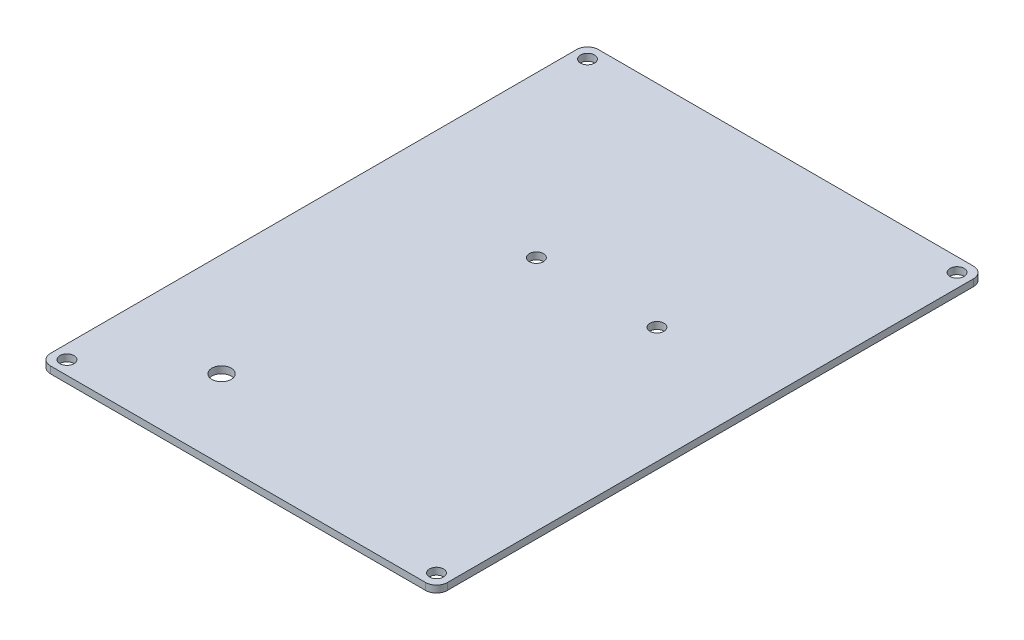
SolidWorks part; units mm, degrees
ref_plane "Front" through (0, 0, 0) normal (0, 0, 1) x (1, 0, 0)
ref_plane "Top" through (0, 0, 0) normal (0, 1, 0) x (1, 0, 0)
ref_plane "Right" through (0, 0, 0) normal (1, 0, 0) x (0, 0, -1)
sketch "Sketch1" plane through (0, 0, 0) normal (0, 1, 0) x (1, 0, 0)
  line L1 (-46, -63.5) -> (46, -63.5)
  line L2 (-46, -63.5) -> (-46, 63.5)
  line L3 (-46, 63.5) -> (46, 63.5)
  line L4 (46, -63.5) -> (46, 63.5)
  line L5 (-46, -63.5) -> (46, 63.5) construction
  line L6 (-46, 63.5) -> (46, -63.5) construction
  point P0 (0, 0)
  dimension "D1" = 127
  dimension "D2" = 92
extrude "Boss-Extrude1" add sketch "Sketch1" along normal blind 1.6
hole_wizard "#4 Clearance Hole2" positions "Sketch2" profile "Sketch3" hole size "#4" standard "ANSI Inch"
sketch "Sketch2" plane through (0, 1.6, 0) normal (0, 1, 0) x (1, 0, 0)
  line L1 (-42.825, 60.325) -> (42.825, 60.325)
  line L2 (-42.825, 60.325) -> (-42.825, -60.325)
  line L3 (-42.825, -60.325) -> (42.825, -60.325)
  line L4 (42.825, 60.325) -> (42.825, -60.325)
  line L5 (-42.825, 60.325) -> (42.825, -60.325) construction
  line L6 (-42.825, -60.325) -> (42.825, 60.325) construction
  line L9 (46, -63.5) -> (46, 63.5) construction
  line L10 (-46, -63.5) -> (46, -63.5) construction
  point P0 (-42.825, 60.325)
  point P2 (42.825, 60.325)
  point P4 (42.825, -60.325)
  point P6 (-42.825, -60.325)
  point P111 (0, 0)
  dimension "D1" = 3.175
  dimension "D2" = 3.175
sketch "Sketch3" plane through (-42.825, 1.6, -60.325) normal (1, 0, 0) x (0, 0, 1)
  line L0 (0, 0) -> (0, 50.9806)
  line L1 (0, 50.9806) -> (1.6319, 50)
  line L2 (1.6319, 50) -> (1.6319, 0)
  line L5 (1.6319, 0) -> (0, 0)
  line L10 (0, 50.9806) -> (-1.632, 50) construction
  line L11 (0, -6.35) -> (0, 107.95) construction
  dimension "Hole Dia." = 3.2639
  dimension "Hole Depth" = 50
  dimension "Drill Angle" = 118
fillet "Fillet1" radius 2.54 4 edges at (46, 0.8, 63.5) (46, 0.8, -63.5) (-46, 0.8, -63.5) (-46, 0.8, 63.5)
hole_wizard "#4 Clearance Hole1" positions "Sketch4" profile "Sketch5" hole size "#4" standard "ANSI Inch"
sketch "Sketch4" plane through (0, 1.6, 0) normal (0, 1, 0) x (1, 0, 0)
  line L1 (46, -60.96) -> (46, 60.96) construction
  line L2 (43.46, 63.5) -> (-43.46, 63.5) construction
  line L3 (-46, 60.96) -> (-46, -60.96) construction
  point P22 (19.05, 14.54)
  point P24 (-8.89, 14.54)
  dimension "D1" = 26.95
  dimension "D2" = 48.96
  dimension "D3" = 48.96
  dimension "D4" = 37.11
sketch "Sketch5" plane through (19.05, 1.6, -14.54) normal (1, 0, 0) x (0, 0, 1)
  line L0 (0, 0) -> (0, 19.7306)
  line L1 (0, 19.7306) -> (1.6319, 18.75)
  line L2 (1.6319, 18.75) -> (1.6319, 0)
  line L5 (1.6319, 0) -> (0, 0)
  line L10 (0, 19.7306) -> (-1.632, 18.75) construction
  line L11 (0, -6.35) -> (0, 107.95) construction
  dimension "Hole Dia." = 3.2639
  dimension "Hole Depth" = 18.75
  dimension "Drill Angle" = 118
hole_wizard "#8 Clearance Hole1" positions "Sketch6" profile "Sketch7" hole size "#8" standard "ANSI Inch"
sketch "Sketch6" plane through (0, 0, 0) normal (0, -1, 0) x (-1, 0, 0)
  circle A0 centre (22.07, -45.25) radius 1.5 construction
  point P0 (22.07, -45.25)
sketch "Sketch7" plane through (-22.07, 0, 45.25) normal (1, 0, 0) x (0, 0, -1)
  line L0 (0, 0) -> (0, 20.1007)
  line L1 (0, 20.1007) -> (2.2479, 18.75)
  line L2 (2.2479, 18.75) -> (2.2479, 0)
  line L5 (2.2479, 0) -> (0, 0)
  line L10 (0, 20.1007) -> (-2.2479, 18.75) construction
  line L11 (0, -6.35) -> (0, 107.95) construction
  dimension "Hole Dia." = 4.4958
  dimension "Hole Depth" = 18.75
  dimension "Drill Angle" = 118
ref_point "PCB_ORIGIN"
sketch "TOP_KEEPOUT" plane through (0, 1.6, 0) normal (0, 1, 0) x (1, 0, 0)
  circle A0 centre (-8.89, 14.54) radius 3.429
  circle A1 centre (19.05, 14.54) radius 3.429
  circle A2 centre (42.825, 60.325) radius 3.429
  circle A3 centre (-42.825, 60.325) radius 3.429
  circle A4 centre (42.825, -60.325) radius 3.429
  circle A5 centre (-42.825, -60.325) radius 3.429
  dimension "D1" = 6.858
sketch "BOTTOM_KEEPOUT" plane through (0, 0, 0) normal (0, -1, 0) x (1, 0, 0)
  line L0 (-26.67, -46.036) -> (-26.67, -3.11) construction
  line L1 (26.67, -47.56) -> (-26.67, -47.56)
  line L2 (26.67, -47.56) -> (26.67, 51.5)
  line L3 (26.67, 51.5) -> (-21.67, 51.5)
  line L4 (-26.67, -47.56) -> (-26.67, 41.5)
  line L7 (-13.716, -47.56) -> (-25.146, -47.56) construction
  line L9 (26.67, -3.11) -> (26.67, -46.56) construction
  line L10 (-25.67, 51.5) -> (25.67, 51.5) construction
  line L11 (-21.67, 51.5) -> (-21.67, 41.5)
  line L12 (-21.67, 41.5) -> (-26.67, 41.5)
  circle A0 centre (-42.825, 60.325) radius 3.937
  circle A1 centre (42.825, 60.325) radius 3.937
  circle A2 centre (42.825, -60.325) radius 3.937
  circle A3 centre (-42.825, -60.325) radius 3.937
  point P13 (0, 0)
  point P20 (26.67, 51.5)
  point P24 (-22.6015, 40.7342)
  dimension "D1" = 7.874
  dimension "D4" = 5
  dimension "D5" = 10
sketch "TOP_CONN_POS" plane through (0, 1.6, 0) normal (0, 1, 0) x (1, 0, 0)
  line L0 (6.35, -35.308) -> (6.35, -45.308)
  line L1 (-37.936, 28.7076) -> (-37.936, 18.7076)
  line L2 (1.35, -40.308) -> (11.35, -40.308)
  line L3 (-42.936, 23.7076) -> (-32.936, 23.7076)
  line L4 (0, 60.436) -> (0, 50.436)
  line L5 (-5, 55.436) -> (5, 55.436)
  line L6 (-37.936, -5.35) -> (-37.936, 52.7652) construction
  line L7 (-43.524, 23.7076) -> (-32.348, 23.7076) construction
  line L8 (0, 61.024) -> (0, 49.848) construction
  line L9 (-29.0576, 55.436) -> (29.0576, 55.436) construction
  line L10 (37.936, 28.7076) -> (37.936, 18.7076)
  line L11 (32.936, 23.7076) -> (42.936, 23.7076)
  line L12 (43.524, 23.7076) -> (32.348, 23.7076) construction
  line L13 (37.936, 52.7652) -> (37.936, -5.35) construction
  line L14 (37.936, -25.0576) -> (37.936, -35.0576)
  line L15 (32.936, -30.0576) -> (42.936, -30.0576)
  line L16 (37.936, -52.7652) -> (37.936, -7.35) construction
  line L17 (43.524, -30.0576) -> (32.348, -30.0576) construction
  line L18 (0, -50.436) -> (0, -60.436)
  line L19 (-5, -55.436) -> (5, -55.436)
  line L20 (29.0576, -55.436) -> (-29.0576, -55.436) construction
  line L21 (0, -61.024) -> (0, -49.848) construction
  line L22 (6.35, -45.896) -> (6.35, -34.72) construction
  line L23 (-16.3576, -40.308) -> (29.0576, -40.308) construction
  point P2 (6.35, -40.308)
  point P5 (0, 0)
  point P6 (-75.0041, 40.9828)
  point P9 (-37.936, 23.7076)
  point P14 (0, 55.436)
  point P17 (-115.78, 17.4589)
  point P18 (-73.2788, 17.3608)
  point P29 (37.936, 23.7076)
  point P32 (73.9745, 24.9368)
  point P40 (37.936, -30.0576)
  point P43 (63.9134, -24.821)
  point P50 (0, -55.436)
  point P53 (6.0715, -69.3479)
  dimension "D1" = 10
  dimension "D2" = 0
  dimension "D3" = 0
  dimension "D4" = 0
  dimension "D5" = 0
  dimension "D6" = 0
  dimension "D7" = 0
  dimension "D8" = 0
  dimension "D9" = 0
  dimension "D10" = 0
  dimension "D11" = 0
  dimension "D12" = 0
  dimension "D13" = 0
sketch "BOTTOM_CONN_POS" plane through (0, 1.6, 0) normal (0, 1, 0) x (1, 0, 0)
  line L0 (0, 12.768) -> (0, -17.232)
  line L1 (-15, -2.232) -> (15, -2.232)
  line L2 (-41.4, 47.425) -> (-41.4, 37.425)
  line L3 (-46.4, 42.425) -> (-36.4, 42.425)
  line L4 (-46, 42.425) -> (-30.6, 42.425) construction
  line L5 (-41.4, 50.75) -> (-41.4, 34.1) construction
  line L6 (-41.4, 28.775) -> (-41.4, 18.775)
  line L7 (-46.4, 23.775) -> (-36.4, 23.775)
  line L8 (-41.4, 13.125) -> (-41.4, 3.125)
  line L9 (-46.4, 8.125) -> (-36.4, 8.125)
  line L10 (-41.4, 0.475) -> (-41.4, -9.525)
  line L11 (-46.4, -4.525) -> (-36.4, -4.525)
  line L12 (-41.4, -12.175) -> (-41.4, -22.175)
  line L13 (-46.4, -17.175) -> (-36.4, -17.175)
  line L14 (-46, 23.775) -> (-30.6, 23.775) construction
  line L15 (-46, 8.125) -> (-30.6, 8.125) construction
  line L16 (-46, -4.525) -> (-30.6, -4.525) construction
  line L17 (-46, -17.175) -> (-30.6, -17.175) construction
  line L18 (-39, -24.8) -> (-39, -34.8)
  line L19 (-44, -29.8) -> (-34, -29.8)
  line L20 (-41.4, -38.925) -> (-41.4, -48.925)
  line L21 (-46.4, -43.925) -> (-36.4, -43.925)
  line L22 (-27.925, -53.9) -> (-27.925, -63.9)
  line L24 (-32.925, -58.9) -> (-22.925, -58.9)
  line L26 (29.425, -53.9) -> (29.425, -63.9)
  line L27 (24.425, -58.9) -> (34.425, -58.9)
  line L28 (29.425, -53.9) -> (29.425, -63.9)
  line L29 (24.425, -58.9) -> (34.425, -58.9)
  line L30 (29.425, -53.9) -> (29.425, -63.9)
  line L31 (24.425, -58.9) -> (34.425, -58.9)
  line L32 (-39, -34.5) -> (-39, -25.1) construction
  line L33 (-42.65, -29.8) -> (-35.5, -29.8) construction
  line L34 (-46, -43.925) -> (-30.92, -43.925) construction
  line L35 (-41.4, -50.75) -> (-41.4, -37.1) construction
  line L36 (-21.1, -58.9) -> (-34.75, -58.9) construction
  line L37 (-27.925, -63.5) -> (-27.925, -48.42) construction
  line L38 (34.75, -58.9) -> (24.1, -58.9) construction
  line L39 (29.425, -63.5) -> (29.425, -48.1) construction
  line L40 (39.35, -41.4) -> (39.35, -51.4)
  line L41 (34.35, -46.4) -> (44.35, -46.4)
  line L42 (41.4, -9.175) -> (41.4, -19.175)
  line L43 (36.4, -14.175) -> (46.4, -14.175)
  line L44 (39.35, -24.3) -> (39.35, -34.3)
  line L45 (34.35, -29.3) -> (44.35, -29.3)
  line L46 (39.35, -39.2) -> (39.35, -53.6) construction
  line L47 (35.85, -46.4) -> (43, -46.4) construction
  line L48 (35.85, -29.3) -> (43, -29.3) construction
  line L49 (41.4, -8.85) -> (41.4, -19.5) construction
  line L50 (46, -14.175) -> (30.6, -14.175) construction
  line L51 (41.4, 3.475) -> (41.4, -6.525)
  line L52 (36.4, -1.525) -> (46.4, -1.525)
  line L53 (41.4, 17.625) -> (41.4, 7.625)
  line L54 (36.4, 12.625) -> (46.4, 12.625)
  line L61 (46, -1.525) -> (30.6, -1.525) construction
  line L62 (46, 12.625) -> (30.92, 12.625) construction
  line L63 (41.4, 33.275) -> (41.4, 23.275)
  line L64 (36.4, 28.275) -> (46.4, 28.275)
  line L65 (46, 28.275) -> (30.92, 28.275) construction
  line L66 (41.4, 48.925) -> (41.4, 38.925)
  line L67 (36.4, 43.925) -> (46.4, 43.925)
  line L68 (46, 43.925) -> (30.92, 43.925) construction
  line L69 (27.975, 63.9) -> (27.975, 53.9)
  line L70 (22.975, 58.9) -> (32.975, 58.9)
  line L71 (21.15, 58.9) -> (34.8, 58.9) construction
  line L72 (27.975, 63.5) -> (27.975, 48.42) construction
  line L73 (10.825, 63.9) -> (10.825, 53.9)
  line L74 (5.825, 58.9) -> (15.825, 58.9)
  line L75 (10.825, 63.5) -> (10.825, 48.1) construction
  line L76 (-7.825, 63.9) -> (-7.825, 53.9)
  line L77 (-12.825, 58.9) -> (-2.825, 58.9)
  line L78 (-7.825, 63.5) -> (-7.825, 48.1) construction
  line L79 (-26.475, 63.9) -> (-26.475, 53.9)
  line L80 (-31.475, 58.9) -> (-21.475, 58.9)
  line L81 (-26.475, 63.5) -> (-26.475, 48.1) construction
  line L82 (0, -51.5) -> (0, 50.1) construction
  line L83 (26.67, -2.232) -> (-26.67, -2.232) construction
  point P4 (0, -2.232)
  point P5 (0, 0)
  point P6 (0, 0)
  point P7 (0, 0)
  point P8 (0, 0)
  point P13 (-41.4, 42.425)
  point P14 (-56.8627, 53.8122)
  point P24 (-41.4, 23.775)
  point P29 (-41.4, 8.125)
  point P34 (-41.4, -4.525)
  point P39 (-41.4, -17.175)
  point P40 (-64.0741, 24.6164)
  point P41 (-64.3674, 8.2002)
  point P42 (-63.6417, -4.1129)
  point P43 (-62.9482, -17.0182)
  point P44 (0, 0)
  point P56 (-39, -29.8)
  point P57 (-74.621, -25.2802)
  point P62 (-41.4, -43.925)
  point P65 (0, 0)
  point P68 (-27.925, -58.9)
  point P71 (0, 0)
  point P72 (0, 0)
  point P73 (-13.6897, -96.2269)
  point P75 (29.425, -58.9)
  point P79 (0, 0)
  point P80 (29.425, -58.9)
  point P84 (-80.3734, -53.1154)
  point P85 (29.425, -58.9)
  point P86 (-34.0917, -85.3365)
  point P87 (0, 0)
  point P100 (29.425, -55.8)
  point P105 (39.35, -46.4)
  point P110 (41.4, -14.175)
  point P115 (39.35, -29.3)
  point P116 (196.5171, -9.1173)
  point P117 (67.9785, -45.0759)
  point P118 (67.9785, -25.5991)
  point P119 (72.9785, -11.994)
  point P135 (41.4, -1.525)
  point P140 (41.4, 12.625)
  point P142 (0, 0)
  point P149 (74.4511, 32.6738)
  point P151 (41.4, 28.275)
  point P152 (63.7321, 38.5888)
  point P154 (0, 0)
  point P156 (74.3822, 8.125)
  point P161 (41.4, 43.925)
  point P162 (64.6558, 47.4543)
  point P169 (27.975, 58.9)
  point P170 (27.5209, 82.675)
  point P179 (10.825, 58.9)
  point P180 (11.0794, 93.6797)
  point P188 (-7.825, 58.9)
  point P189 (-12.9879, 81.2849)
  point P190 (-11.684, 63.9)
  point P197 (-26.475, 58.9)
  point P198 (-22.925, 83.3816)
  point P201 (2.5032, -5.6713)
  dimension "D1" = 30
  dimension "D2" = 10
  dimension "D3" = 0
  dimension "D4" = 0
  dimension "D5" = 10
  dimension "D6" = 10
  dimension "D7" = 10
  dimension "D8" = 10
  dimension "D9" = 0
  dimension "D10" = 0
  dimension "D11" = 0
  dimension "D12" = 0
  dimension "D13" = 10
  dimension "D14" = 10
  dimension "D15" = 10
  dimension "D16" = 0
  dimension "D17" = 0
  dimension "D18" = 0
  dimension "D19" = 0
  dimension "D20" = 0
  dimension "D21" = 0
  dimension "D22" = 0
  dimension "D23" = 0
  dimension "D24" = 0
  dimension "D25" = 0
  dimension "D26" = 0
  dimension "D27" = 0
  dimension "D28" = 0
  dimension "D29" = 10
  dimension "D30" = 10
  dimension "D31" = 0
  dimension "D32" = 0
  dimension "D33" = 10
  dimension "D34" = 0
  dimension "D35" = 10
  dimension "D36" = 0
  dimension "D37" = 10
  dimension "D38" = 0
  dimension "D39" = 0
  dimension "D40" = 10
  dimension "D41" = 0
  dimension "D42" = 10
  dimension "D43" = 0
  dimension "D44" = 10
  dimension "D45" = 0
  dimension "D46" = 0
  dimension "D47" = 0
